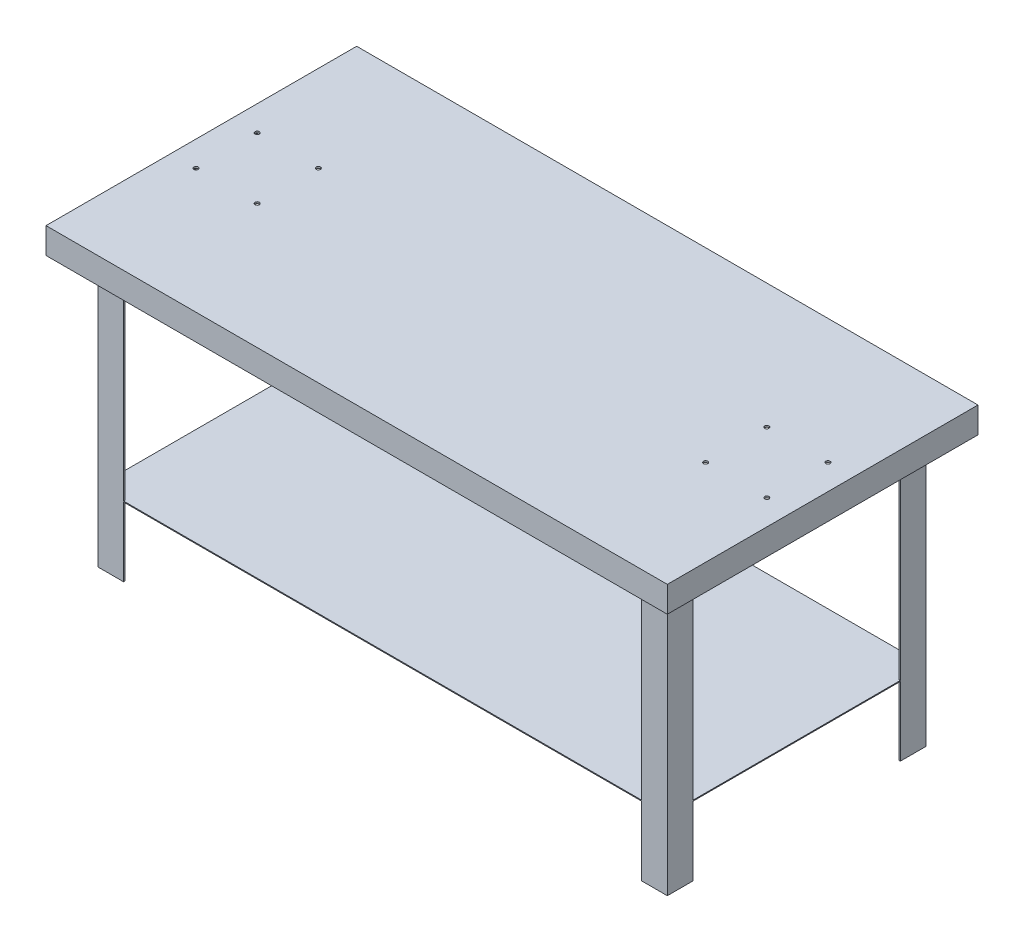
SolidWorks part; units mm, degrees
material "1023 Carbon Steel Sheet (SS)"
ref_plane "Front Plane" through (0, 0, 0) normal (0, 0, 1) x (1, 0, 0)
ref_plane "Top Plane" through (0, 0, 0) normal (0, 1, 0) x (1, 0, 0)
ref_plane "Right Plane" through (0, 0, 0) normal (1, 0, 0) x (0, 0, -1)
sketch "Sketch1" plane through (0, 0, 0) normal (1, 0, 0) x (0, 0, -1)
  line L0 (0, -1534.4769) -> (0, 75189.3682) construction
  line L1 (-457.2, 0) -> (457.2, 0)
  line L2 (457.2, 0) -> (457.2, -76.2)
  line L3 (457.2, -76.2) -> (381, -76.2)
  line L4 (-457.2, -76.2) -> (-381, -76.2)
  line L5 (-457.2, 0) -> (-457.2, -76.2)
  line L6 (-452.4375, -71.4375) -> (-381, -71.4375)
  line L7 (-452.4375, -4.7625) -> (-452.4375, -71.4375)
  line L8 (-452.4375, -4.7625) -> (452.4375, -4.7625)
  line L9 (452.4375, -4.7625) -> (452.4375, -71.4375)
  line L10 (452.4375, -71.4375) -> (381, -71.4375)
  line L11 (-381, -71.4375) -> (-381, -76.2)
  line L12 (381, -71.4375) -> (381, -76.2)
  point P10 (0, 0)
  dimension "D1" = 76.2
  dimension "D2" = 76.2
  dimension "D3" = 914.4
  dimension "D4" = 4.7625
extrude "Boss-Extrude1" add sketch "Sketch1" along normal mid plane 1828.8
sketch "Sketch2" plane through (0, 0, 0) normal (0, 0, 1) x (1, 0, 0)
  line L0 (0, -1000) -> (0, 49000) construction
  line L1 (-914.4, 0) -> (-914.4, -76.2)
  line L2 (-914.4, -76.2) -> (-838.2, -76.2)
  line L3 (914.4, -76.2) -> (-914.4, -76.2) construction
  line L4 (-838.2, -76.2) -> (-838.2, -71.4375)
  line L5 (-838.2, -71.4375) -> (-909.6375, -71.4375)
  line L6 (-909.6375, -71.4375) -> (-909.6375, 0)
  line L7 (914.4, 0) -> (-914.4, 0) construction
  line L8 (-909.6375, 0) -> (-914.4, 0)
  line L9 (909.6375, 0) -> (914.4, 0)
  line L10 (909.6375, -71.4375) -> (909.6375, 0)
  line L11 (838.2, -71.4375) -> (909.6375, -71.4375)
  line L12 (838.2, -76.2) -> (838.2, -71.4375)
  line L13 (914.4, -76.2) -> (838.2, -76.2)
  line L14 (914.4, 0) -> (914.4, -76.2)
  dimension "D1" = 4.7625
extrude "Boss-Extrude2" add sketch "Sketch2" along normal mid plane 914.4
sketch "Sketch3" plane through (0, 0, 0) normal (0, 1, 0) x (1, 0, 0)
  line L1 (-840, 90) -> (-660, 90)
  line L2 (-840, 90) -> (-840, -90)
  line L3 (-840, -90) -> (-660, -90)
  line L4 (-660, 90) -> (-660, -90)
  line L5 (-750, -90) -> (-750, 90) construction
  line L6 (-840, 0) -> (-660, 0) construction
  point P0 (-750, 0)
  dimension "D1" = 180
  dimension "D2" = 750
split line "Split Line1" [suppressed]
sketch "Sketch4" plane through (0, -4.7625, 0) normal (0, -1, 0) x (1, 0, 0)
  line L0 (0, -1000) -> (0, 49000) construction
  line L1 (-1000, 0) -> (49000, 0) construction
  line L2 (-762, 381) -> (-838.2, 381)
  line L3 (838.2, 381) -> (-838.2, 381) construction
  line L4 (-838.2, 381) -> (-838.2, 304.8)
  line L5 (-838.2, 381) -> (-838.2, -381) construction
  line L6 (-838.2, 304.8) -> (-833.646, 304.8)
  line L7 (-833.646, 304.8) -> (-833.646, 376.446)
  line L8 (-833.646, 376.446) -> (-762, 376.446)
  line L9 (-762, 376.446) -> (-762, 381)
  line L10 (-833.646, -376.446) -> (-762, -376.446)
  line L11 (-833.646, -304.8) -> (-833.646, -376.446)
  line L12 (-838.2, -304.8) -> (-833.646, -304.8)
  line L13 (-838.2, -381) -> (-838.2, -304.8)
  line L14 (-762, -381) -> (-838.2, -381)
  line L15 (-762, -376.446) -> (-762, -381)
  line L16 (833.646, -304.8) -> (833.646, -376.446)
  line L17 (838.2, -304.8) -> (833.646, -304.8)
  line L18 (838.2, -381) -> (838.2, -304.8)
  line L19 (762, -381) -> (838.2, -381)
  line L20 (762, -376.446) -> (762, -381)
  line L21 (833.646, -376.446) -> (762, -376.446)
  line L22 (833.646, 376.446) -> (762, 376.446)
  line L23 (833.646, 304.8) -> (833.646, 376.446)
  line L24 (838.2, 304.8) -> (833.646, 304.8)
  line L25 (838.2, 381) -> (838.2, 304.8)
  line L26 (762, 381) -> (838.2, 381)
  line L27 (762, 376.446) -> (762, 381)
  dimension "D1" = 4.554
  dimension "D2" = 76.2
extrude "Boss-Extrude3" add sketch "Sketch4" along normal offset from surface (865.1875 mm away) 869.95 up to face at (0, 0, 0)
sketch "Sketch5" plane through (0, -4.7625, 0) normal (0, -1, 0) x (1, 0, 0)
  line L1 (-838.2, 381) -> (838.2, 381)
  line L2 (-838.2, 381) -> (-838.2, -381)
  line L3 (-838.2, -381) -> (838.2, -381)
  line L4 (838.2, 381) -> (838.2, -381)
extrude "Boss-Extrude4" add sketch "Sketch5" against normal blind 2.657 from offset 661.9875
sketch "Sketch6" plane through (0, 0, 0) normal (0, 1, 0) x (1, 0, 0)
  line L0 (0, -1000) -> (0, 49000) construction
  line L3 (-840, -90) -> (-660, -90) construction
  line L4 (-840, -90) -> (-840, 90) construction
  line L5 (-840, 90) -> (-660, 90) construction
  line L6 (-660, -90) -> (-660, 90) construction
  line L7 (-750, 90) -> (-750, -90) construction
  line L8 (-840, 0) -> (-660, 0) construction
  circle A0 centre (-840, 90) radius 6.35
  circle A1 centre (-660, 90) radius 6.35
  circle A2 centre (-840, -90) radius 6.35
  circle A3 centre (-660, -90) radius 6.35
  circle A4 centre (660, -90) radius 6.35
  circle A5 centre (840, -90) radius 6.35
  circle A6 centre (840, 90) radius 6.35
  circle A7 centre (660, 90) radius 6.35
  point P4 (-750, 0)
  dimension "D3" = 12.7
  dimension "D1" = 180
  dimension "D2" = 750
extrude "Cut-Extrude1" cut sketch "Sketch6" against normal blind 10
